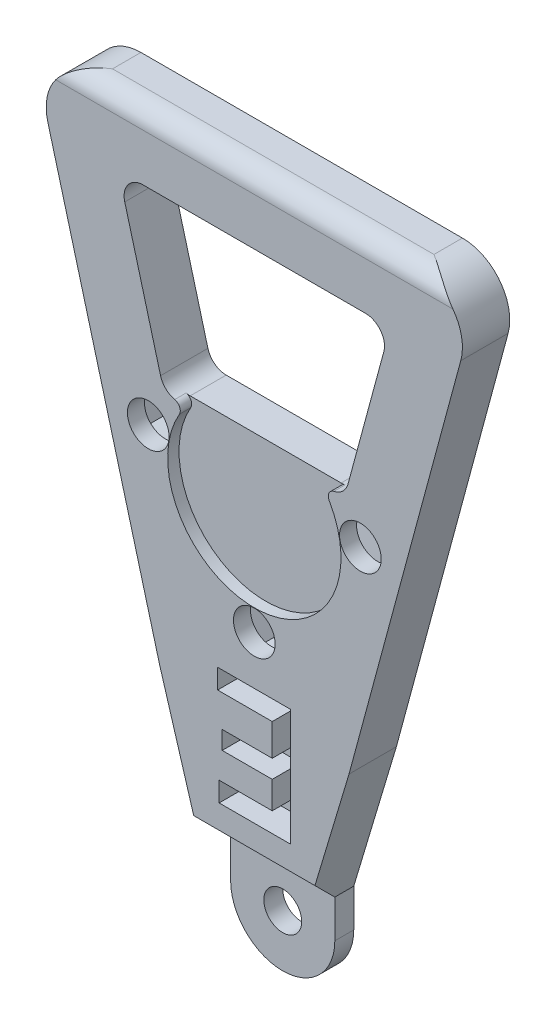
SolidWorks part; units mm, degrees
ref_plane "Front Plane" through (0, 0, 0) normal (0, 0, 1) x (1, 0, 0)
ref_plane "Top Plane" through (0, 0, 0) normal (0, 1, 0) x (1, 0, 0)
ref_plane "Right Plane" through (0, 0, 0) normal (1, 0, 0) x (0, 0, -1)
sketch "Sketch1" plane through (0, 0, 0) normal (0, 0, 1) x (1, 0, 0)
  line L0 (-23.5, 25) -> (23.5, 25)
  line L1 (23.5, 25) -> (10, -25)
  line L2 (10, -25) -> (-10, -25)
  line L3 (-10, -25) -> (-23.5, 25)
  point P2 (0, 25)
  point P5 (0, -25)
  point P7 (-16.75, 0)
  dimension "D1" = 47
  dimension "D2" = 50
  dimension "D3" = 20
extrude "Boss-Extrude1" add sketch "Sketch1" along normal blind 5
sketch "Sketch2" plane through (0, 0, 5) normal (0, 0, 1) x (1, 0, 0)
  line L4 (-9.4993, 0) -> (9.4993, 0)
  line L5 (-10, -25) -> (10, -25) construction
  line L8 (-14.3593, 18) -> (-4.6393, -18)
  line L9 (-4.6393, -18) -> (4.6393, -18)
  line L10 (4.6393, -18) -> (14.3593, 18)
  line L11 (14.3593, 18) -> (-14.3593, 18)
  line L12 (-14.3593, 18) -> (-9.4993, 0)
  line L14 (9.4993, 0) -> (14.3593, 18)
  line L15 (14.3593, 18) -> (-14.3593, 18)
  dimension "D2" = 25
  dimension "D1" = 7
extrude "Cut-Extrude1" cut sketch "Sketch2" against normal up to next
sketch "Sketch5" plane through (0, 0, 5) normal (0, 0, 1) x (1, 0, 0)
  line L2 (-9.4993, 0) -> (9.4993, 0) construction
  circle A0 centre (0, -5.65) radius 9.15
  dimension "D1" = 18.3
  dimension "D2" = 3.5
extrude "Cut-Extrude3" cut sketch "Sketch5" against normal blind 1.2
sketch "Sketch6" plane through (0, 0, 5) normal (0, 0, 1) x (1, 0, 0)
  line L0 (-10, -25) -> (10, -25) construction
  line L1 (-11.1978, -3.65) -> (11.1978, -3.65) construction
  line L4 (0, 0) -> (0, -25) construction
  line L5 (7.1972, 0) -> (-7.1972, 0) construction
  circle A0 centre (-11.1978, -3.65) radius 2.2
  circle A1 centre (0, -5.65) radius 11.375 construction
  circle A2 centre (0, -17.025) radius 2.2
  circle A5 centre (11.1978, -3.65) radius 2.2
  dimension "D1" = 4.4
  dimension "D3" = 22.75
  dimension "D2" = 2
extrude "Cut-Extrude4" cut sketch "Sketch6" against normal up to next
sketch "Sketch7" plane through (0, 0, 0) normal (0, 0, -1) x (-1, 0, 0)
  line L0 (-10, -25) -> (-23.5, 25) construction
  line L1 (-7.2084, -4.7108) -> (-8.2844, -0.7254)
  line L2 (-8.2844, -0.7254) -> (-12.2738, 0.3353)
  line L3 (-12.2738, 0.3353) -> (-15.1872, -2.5892)
  line L4 (-15.1872, -2.5892) -> (-14.1112, -6.5746)
  line L5 (-14.1112, -6.5746) -> (-10.1218, -7.6353)
  line L6 (-10.1218, -7.6353) -> (-7.2084, -4.7108)
  line L8 (-4.1281, -17.025) -> (-2.064, -20.6)
  line L9 (-2.064, -20.6) -> (2.064, -20.6)
  line L10 (2.064, -20.6) -> (4.1281, -17.025)
  line L11 (4.1281, -17.025) -> (2.064, -13.45)
  line L12 (2.064, -13.45) -> (-2.064, -13.45)
  line L13 (-2.064, -13.45) -> (-4.1281, -17.025)
  line L14 (10.1218, -7.6353) -> (14.1112, -6.5746)
  line L15 (14.1112, -6.5746) -> (15.1872, -2.5892)
  line L16 (15.1872, -2.5892) -> (12.2738, 0.3353)
  line L17 (12.2738, 0.3353) -> (8.2844, -0.7254)
  line L18 (8.2844, -0.7254) -> (7.2084, -4.7108)
  line L19 (7.2084, -4.7108) -> (10.1218, -7.6353)
  line L21 (23.5, 25) -> (10, -25) construction
  circle A0 centre (-11.1978, -3.65) radius 3.575 construction
  circle A1 centre (0, -17.025) radius 3.575 construction
  circle A2 centre (11.1978, -3.65) radius 3.575 construction
  circle A4 centre (-11.1978, -3.65) radius 2.2 construction
  dimension "D1" = 7.15
  dimension "D2" = 7.15
  dimension "D3" = 7.15
extrude "Cut-Extrude5" cut sketch "Sketch7" against normal blind 3.2
sketch "Sketch8" plane through (0, -25, 0) normal (0, -1, 0) x (1, 0, 0)
  line L1 (-10, 5) -> (10, 5)
  line L2 (-10, 5) -> (-10, 0)
  line L3 (-10, 0) -> (10, 0)
  line L4 (10, 5) -> (10, 0)
extrude "Boss-Extrude2" add sketch "Sketch8" along normal blind 15
sketch "Sketch3" plane through (0, 0, 5) normal (0, 0, 1) x (1, 0, 0)
  line L0 (-5.5, -44) -> (-5.5, -40)
  line L2 (-5.5, -40) -> (5.5, -40)
  line L3 (5.5, -40) -> (5.5, -44)
  line L4 (10, -40) -> (-10, -40) construction
  arc A0 (-5.5, -44) -> (5.5, -44) centre (0, -44) ccw
  circle A1 centre (0, -44) radius 2
  dimension "D1" = 11
  dimension "D2" = 3.5
  dimension "D3" = 4
extrude "Boss-Extrude3" add sketch "Sketch3" against normal up to surface (5 mm away) up to face at (-11.1978, -3.65, 0)
sketch "Sketch9" plane through (0, 0, 0) normal (0, 0, -1) x (-1, 0, 0)
  line L0 (-10, -25) -> (-5.5, -40)
  line L1 (-5.5, -40) -> (-10, -40)
  line L2 (-10, -40) -> (-10, -25)
  line L3 (10, -25) -> (5.5, -40)
  line L4 (5.5, -40) -> (10, -40)
  line L5 (10, -40) -> (10, -25)
extrude "Cut-Extrude6" cut sketch "Sketch9" against normal up to next
fillet "Fillet2" radius 2 4 edges at (9.4993, 0, 2.5) (14.3593, 18, 2.5) (-9.4993, 0, 2.5) (-14.3593, 18, 2.5)
sketch "Sketch10" [suppressed] plane through (0, 0, 2.5) normal (0, 0, -1) x (-1, 0, 0)
  circle A0 centre (-11.3377, -3.6) radius 1.96
  circle A1 centre (11.3377, -3.6) radius 1.96
  circle A2 centre (6.5172, -15) radius 1.96
  circle A3 centre (-6.5172, -15) radius 1.96
  circle A4 centre (-11.3377, -3.6) radius 1.96 construction
extrude "Boss-Extrude4" [suppressed] add sketch "Sketch10" against normal blind 0.5
sketch "Sketch12" plane through (0, 0, 5) normal (0, 0, 1) x (1, 0, 0)
  text T0 "<b><r180>E</r></b>" font "Arial Narrow" height in points 48
extrude "Cut-Extrude7" cut sketch "Sketch12" against normal blind 3
sketch "Sketch13" plane through (-5.5, 0, 0) normal (-1, 0, 0) x (0, 0, 1)
  line L0 (5, -37) -> (2, -40)
  line L2 (2, -40) -> (2, -51.8661)
  line L3 (2, -51.8661) -> (5, -51.8661)
  line L4 (5, -51.8661) -> (5, -37)
  line L5 (0, -40) -> (0, -44) construction
  line L6 (0, -40) -> (5, -40) construction
  line L7 (5, -40) -> (5, -44) construction
  dimension "D1" = 2
  dimension "D2" = 45
extrude "Cut-Extrude8" cut sketch "Sketch13" against normal mid plane 25
fillet "Fillet3" radius 5 2 edges at (-23.5, 25, 2.5) (23.5, 25, 2.5) tangent propagation no
fillet "Fillet4" radius 2 1 edges at (0, 25, 5) tangent propagation no
fillet "Fillet5" radius 0.75 2 edges at (-7.1972, 0, 4.4) (7.1972, 0, 4.4)
